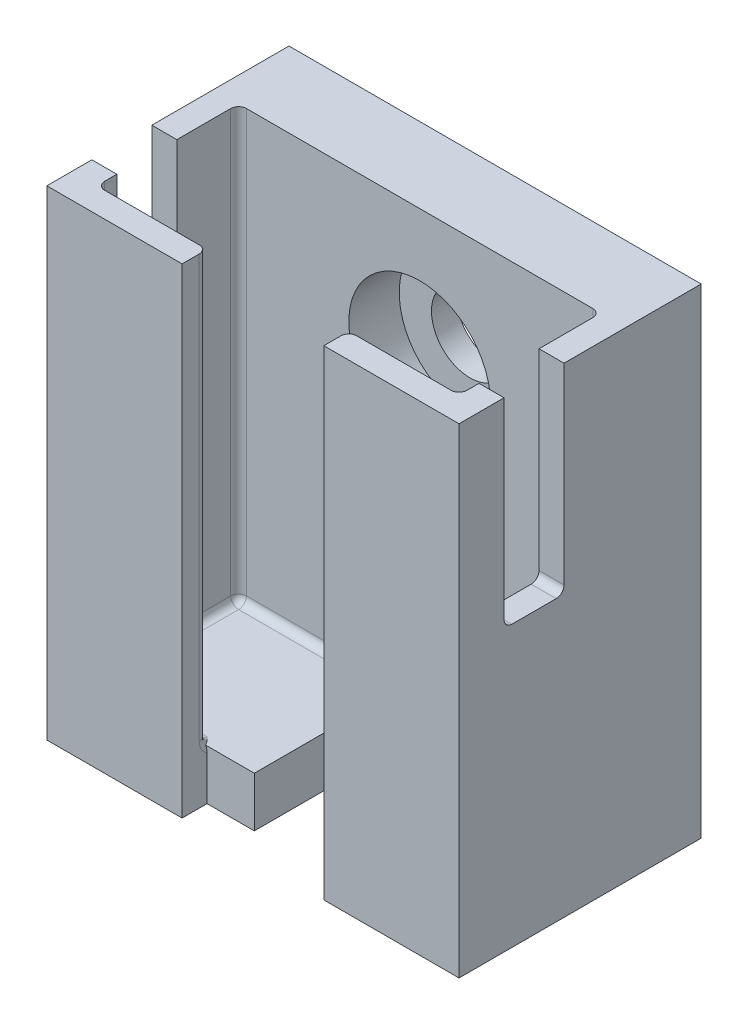
SolidWorks part; units mm, degrees
ref_plane "Front Plane" through (0, 0, 0) normal (0, 0, 1) x (1, 0, 0)
ref_plane "Top Plane" through (0, 0, 0) normal (0, 1, 0) x (1, 0, 0)
ref_plane "Right Plane" through (0, 0, 0) normal (1, 0, 0) x (0, 0, -1)
sketch "Sketch1" plane through (0, 0, 0) normal (0, 1, 0) x (1, 0, 0)
  line L0 (4.5, -6.1) -> (4.5, -7.6875)
  line L1 (-11.5, 6.1) -> (11.5, 6.1)
  line L2 (-11.5, 6.1) -> (-11.5, -6.1)
  line L3 (-11.5, -6.1) -> (-4.5, -6.1)
  line L4 (11.5, 6.1) -> (11.5, -6.1)
  line L5 (-11.5, 6.1) -> (11.5, -6.1) construction
  line L6 (-11.5, -6.1) -> (11.5, 6.1) construction
  line L7 (-13.088, -7.6875) -> (-4.5, -7.6875)
  line L8 (-13.088, -7.6875) -> (-13.088, 7.6875)
  line L9 (-13.088, 7.6875) -> (13.088, 7.6875)
  line L10 (13.088, -7.6875) -> (13.088, 7.6875)
  line L11 (-13.088, -7.6875) -> (13.088, 7.6875) construction
  line L12 (-13.088, 7.6875) -> (13.088, -7.6875) construction
  line L13 (0, -8.4563) -> (0, 8.4563) construction
  line L14 (-4.5, -6.1) -> (-4.5, -7.6875)
  line L15 (4.5, -7.6875) -> (13.088, -7.6875)
  line L16 (4.5, -6.1) -> (11.5, -6.1)
  point P0 (0, 0)
  point P6 (0, 0)
  dimension "D1" = 23
  dimension "D2" = 12.2
  dimension "D3" = 1.588
  dimension "D4" = 1.5875
  dimension "D5" = 4.5
extrude "Boss-Extrude1" add sketch "Sketch1" along normal blind 30.48
sketch "Sketch2" plane through (0, 0, 0) normal (0, -1, 0) x (1, 0, 0)
  line L5 (11.5, 6.1) -> (4.5, 6.1) construction
  line L11 (11.5, 0) -> (11.5, 6.1)
  line L12 (11.5, 6.1) -> (9.5, 6.1)
  line L13 (-1.5, 0) -> (9.5, 0)
  line L14 (-1.5, 0) -> (-1.5, 6.1)
  line L17 (-11.5, 6.1) -> (-1.5, 6.1)
  line L18 (-11.5, 6.1) -> (-11.5, -6.1)
  line L19 (-11.5, -6.1) -> (11.5, -6.1)
  line L20 (11.5, 0) -> (11.5, -6.1)
  line L21 (9.5, 0) -> (9.5, 6.1)
  dimension "D1" = 1.5
  dimension "D2" = 2
extrude "Boss-Extrude2" add sketch "Sketch2" against normal blind 3.175
sketch "Sketch3" plane through (0, 30.48, 0) normal (0, 1, 0) x (1, 0, 0)
  line L18 (-13.088, 7.6875) -> (-13.088, -7.6875) construction
  line L21 (-9.652, -1.02) -> (-13.088, -1.02)
  line L22 (-9.652, -1.02) -> (-9.652, -4.83)
  line L23 (-9.652, -4.83) -> (-13.088, -4.83)
  line L24 (-13.088, -1.02) -> (-13.088, -4.83)
  point P10 (-13.088, -2.925)
  dimension "D1" = 3.81
  dimension "D2" = 3.175
extrude "Cut-Extrude1" cut sketch "Sketch3" against normal blind 12.7
mirror "Mirror1" about plane through (0, 0, 0) normal (1, 0, 0) of "Cut-Extrude1"
sketch "Sketch5" plane through (0, 0, -7.6875) normal (0, 0, -1) x (-1, 0, 0)
  line L0 (8.4563, 0) -> (-8.4563, 0) construction
  line L1 (-13.088, 30.48) -> (13.088, 30.48) construction
  circle A0 centre (0, 8.4667) radius 2.45
  circle A1 centre (0, 22.0133) radius 2.45
  dimension "D1" = 4.9
  dimension "D2" = 4.9
  dimension "D3" = 8.4667
  dimension "D4" = 8.4667
extrude "Cut-Extrude2" cut sketch "Sketch5" against normal up to surface (1.5875 mm away) up to face at (0, 16.8275, -6.1)
sketch "Sketch6" plane through (0, 0, -6.1) normal (0, 0, 1) x (1, 0, 0)
  line L4 (-11.5, 3.175) -> (11.5, 3.175)
  line L6 (11.5, 3.175) -> (11.5, 30.48)
  line L7 (11.5, 30.48) -> (-11.5, 30.48)
  line L8 (-11.5, 30.48) -> (-11.5, 3.175)
  line L10 (11.5, 3.175) -> (11.5, 30.48)
  line L11 (11.5, 30.48) -> (-11.5, 30.48)
  line L12 (-11.5, 30.48) -> (-11.5, 3.175)
  line L14 (-11.5, 3.175) -> (11.5, 3.175)
  circle A0 centre (0, 22.0133) radius 4.5
  circle A1 centre (0, 8.4667) radius 4.5
  dimension "D1" = 9
  dimension "D2" = 9
  dimension "D3" = 0
extrude "Boss-Extrude3" add sketch "Sketch6" along normal blind 3.2
fillet "Fillet3" radius 0.5 4 edges at (0, 3.175, -2.9) (11.5, 16.8275, 6.1) (11.5, 16.8275, -2.9) (11.5, 3.175, 1.6)
fillet "Fillet1" radius 0.5 5 edges at (-11.5, 3.175, 1.85) (-8, 3.175, 6.1) (4.5, 15.24, 6.1) (-11.5, 17.0775, -2.9) (-11.5, 3.3214, -2.7536)
fillet "Fillet5" radius 0.5 6 edges at (-4.5, 17.0775, 6.1) (-4.5, 3.3214, 5.9536) (-12.294, 17.78, 4.83) (-12.294, 17.78, 1.02) (12.294, 17.78, 1.02) (12.294, 17.78, 4.83)
fillet "Fillet4" radius 0.5 2 edges at (-11.5, 17.0775, 6.1) (-11.3536, 3.3214, 5.9536)
fillet "Fillet6" radius 0.5 5 edges at (11.3536, 3.3214, 5.9536) (10.25, 3.175, 6.1) (9.5, 1.5875, 6.1) (9.5, 1.5875, 0) (-1.5, 1.5875, 0)
